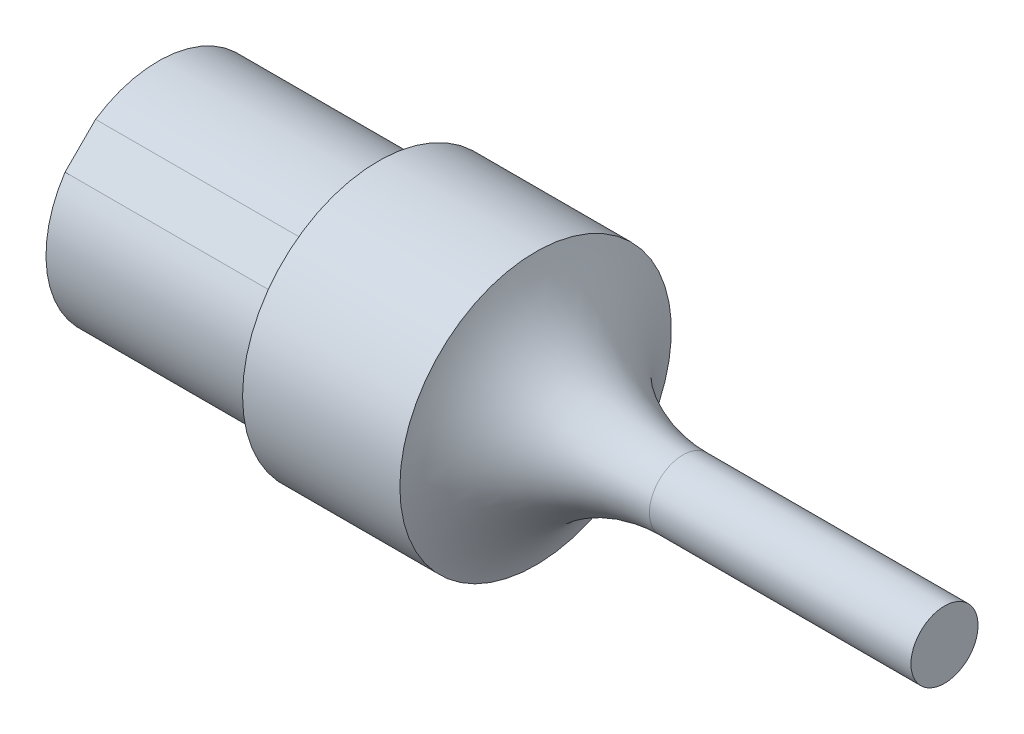
SolidWorks part; units mm, degrees
ref_plane "前视基准面" through (0, 0, 0) normal (0, 0, 1) x (1, 0, 0)
ref_plane "上视基准面" through (0, 0, 0) normal (0, 1, 0) x (1, 0, 0)
ref_plane "右视基准面" through (0, 0, 0) normal (1, 0, 0) x (0, 0, -1)
sketch "草图1" plane through (0, 0, 0) normal (0, 1, 0) x (1, 0, 0)
  line L0 (-32.682, -1.5351) -> (56.0582, -1.5351) construction
  line L1 (-32.682, 5.598) -> (-18.682, 5.598)
  line L2 (-32.682, 5.598) -> (-32.682, -9.402)
  line L3 (-32.682, -9.402) -> (-18.682, -9.402)
  line L4 (-18.682, 5.598) -> (-18.682, -9.402)
  line L5 (-18.682, 7.098) -> (-8.682, 7.098)
  line L6 (-18.682, 7.098) -> (-18.682, -10.902)
  line L7 (-18.682, -10.902) -> (-8.682, -10.902)
  line L8 (-8.682, 7.098) -> (-8.682, -10.902)
  line L9 (-8.682, -4.402) -> (17.318, -4.402)
  line L10 (-8.682, -4.402) -> (-8.682, 0.598)
  line L11 (-8.682, 0.598) -> (17.318, 0.598)
  line L12 (17.318, -4.402) -> (17.318, 0.598)
  point P12 (-18.682, -1.902)
  point P13 (-18.682, -1.902)
  point P14 (-8.682, -1.902)
  dimension "D1" = 14
  dimension "D2" = 15
  dimension "D3" = 18
  dimension "D4" = 10
  dimension "D5" = 50
  dimension "D6" = 5
revolve "旋转1" add sketch "草图1" angle 360 about L0 region at (-25.682, 0, -2.0315) region at (-13.682, 0, -2.7815) region at (4.318, 0, 0.4685)
fillet "圆角1" radius 10 1 edges at (-8.682, 0, 3.6682)
sketch "草图2" plane through (-32.682, 0, 0) normal (-1, 0, 0) x (0, 0, 1)
  line L0 (5.515, 5.9196) -> (7.4546, 3.9799)
  circle A0 centre (1.5351, 0) radius 7.1331 construction
  circle A1 centre (1.5351, 0) radius 7.1331 construction
  dimension "D1" = 7
extrude "切除-拉伸-薄壁1" cut sketch "草图2" against normal up to surface (14 mm away) thin up to face at (-18.682, 0, 8.6682) thin type one direction reverse wall 10
